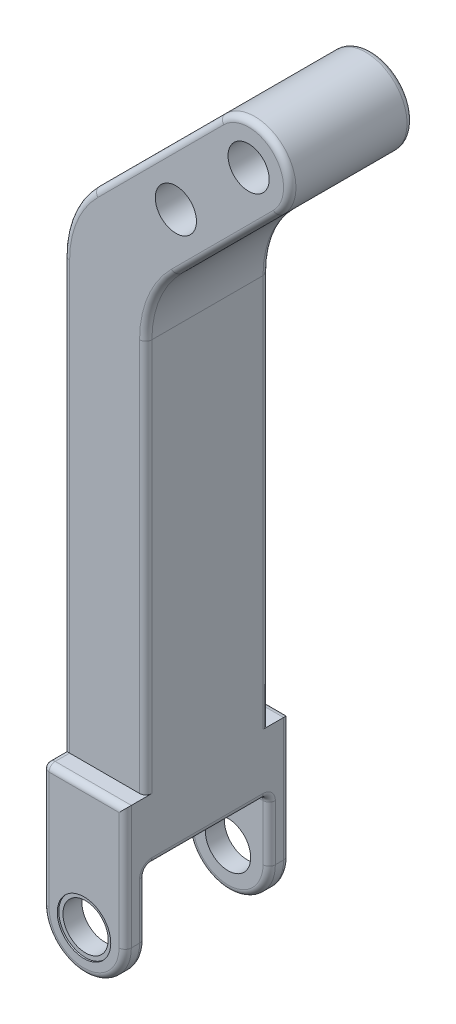
SolidWorks part; units mm, degrees
material "6061 合金"
ref_plane "前视基准面" through (0, 0, 0) normal (0, 0, 1) x (1, 0, 0)
ref_plane "上视基准面" through (0, 0, 0) normal (0, 1, 0) x (1, 0, 0)
ref_plane "右视基准面" through (0, 0, 0) normal (1, 0, 0) x (0, 0, -1)
other "Configuration Table"
sketch "草图1" plane through (0, 0, 0) normal (0, 0, 1) x (1, 0, 0)
  circle A0 centre (0, 0) radius 20
  circle A1 centre (0, 0) radius 10
  dimension "D1" = 40
  dimension "D2" = 20
extrude "凸台-拉伸1" add sketch "草图1" along normal blind 60 contours A1 | A0 region at (0, 0, 0)
ref_plane "基准面1" through (0, 0, 30) normal (0, 0, 1) x (1, 0, 0)
sketch "草图2" plane through (0, 0, 30) normal (0, 0, 1) x (1, 0, 0)
  line L0 (0, 0) -> (-70, -70) construction
  line L1 (-70, -70) -> (-70, -320) construction
  line L2 (0, -57.3148) -> (0, 49.9409) construction
  line L3 (-56.8582, 0) -> (46.4003, 0) construction
  line L4 (-14.1421, 14.1421) -> (-90, -61.7157)
  line L5 (14.1421, -14.1421) -> (-50, -78.2843)
  line L6 (-90, -61.7157) -> (-90, -320)
  line L7 (-50, -78.2843) -> (-50, -320)
  line L8 (-90, -320) -> (-50, -320)
  circle A2 centre (0, 0) radius 20 construction
  arc A3 (-14.1421, 14.1421) -> (14.1421, -14.1421) centre (0, 0) ccw
  dimension "D1" = 45
  dimension "D2" = 250
  dimension "D3" = 70
  dimension "D4" = 40
  dimension "D5" = 40
extrude "凸台-拉伸2" add sketch "草图2" along normal mid plane 60 contours L7 L8 L6 L4 A3 L5
sketch "草图4" plane through (0, 0, 60) normal (0, 0, 1) x (1, 0, 0)
  line L0 (-90, -61.7157) -> (-90, -320) construction
  line L1 (-90, -290) -> (-50, -290)
  line L2 (-90, -290) -> (-90, -350)
  line L4 (-50, -290) -> (-50, -350)
  line L5 (-50, -78.2843) -> (-50, -320) construction
  line L6 (-90, -320) -> (-50, -320) construction
  arc A0 (-90, -350) -> (-50, -350) centre (-70, -350) ccw
  circle A1 centre (-70, -350) radius 11
  dimension "D3" = 22
  dimension "D1" = 30
  dimension "D2" = 30
extrude "凸台-拉伸3" add sketch "草图4" along normal blind 10
mirror "镜向1" about plane through (0, 0, 30) normal (0, 0, 1) of "凸台-拉伸3"
sketch "草图5" plane through (0, 0, 0) normal (0, 1, 0) x (1, 0, 0)
  line L0 (0, 0) -> (0, -78.0582) construction
ref_plane "基准面2" through (-70, 0, 0) normal (-1, 0, 0) x (0, 0, 1)
sketch "草图7" plane through (-70, 0, 0) normal (-1, 0, 0) x (0, 0, 1)
  line L0 (-34.1239, -350) -> (109.535, -350) construction
sketch "草图8" plane through (0, 0, 60) normal (0, 0, 1) x (1, 0, 0)
  line L0 (0, 0) -> (-70, -70) construction
  circle A0 centre (-35.3553, -35.3553) radius 10
  dimension "D1" = 20
  dimension "D2" = 50
extrude "切除-拉伸1" cut sketch "草图8" against normal blind 100
fillet "圆角1" radius 50 2 edges at (-90, -61.7157, 30) (-50, -78.2843, 30)
fillet "圆角2" radius 3 34 edges at (-50, -320, 70) (-70, -370, 70) (-50, -335, 60) (-70, -370, 60) (-50, -335, 0) (-70, -370, 0) (-50, -320, -10) (-70, -370, -10) (-70, -320, 60) (-50, -320, 30) (-70, -320, 0) (-90, -290, 65) (-90, -320, 70) (-90, -335, 60) (-90, -320, 30) (-90, -335, 0) (-90, -320, -10) (-90, -290, -5) (-50, -194.4975, 0) (-46.194, -79.8608, 0) (-10.6066, -38.8909, 0) (14.1421, 14.1421, 0) (-44.7487, -16.4645, 0) (-86.194, -63.2922, 0) (-90, -186.2132, 0) (14.1421, 14.1421, 60) (-10.6066, -38.8909, 60) (-46.194, -79.8608, 60) (-50, -194.4975, 60) (-90, -186.2132, 60) (-86.194, -63.2922, 60) (-44.7487, -16.4645, 60) (-70, -290, 70) (-70, -290, -10)
sketch "草图9" plane through (0, 0, 70) normal (0, 0, 1) x (1, 0, 0)
  circle A0 centre (-70, -350) radius 13
  dimension "D1" = 26
extrude "切除-拉伸2" cut sketch "草图9" against normal blind 0.75
sketch "草图10" plane through (0, 0, -10) normal (0, 0, -1) x (-1, 0, 0)
  circle A0 centre (70, -350) radius 13
  dimension "D1" = 26
extrude "切除-拉伸3" cut sketch "草图10" against normal blind 0.75 contours A0
